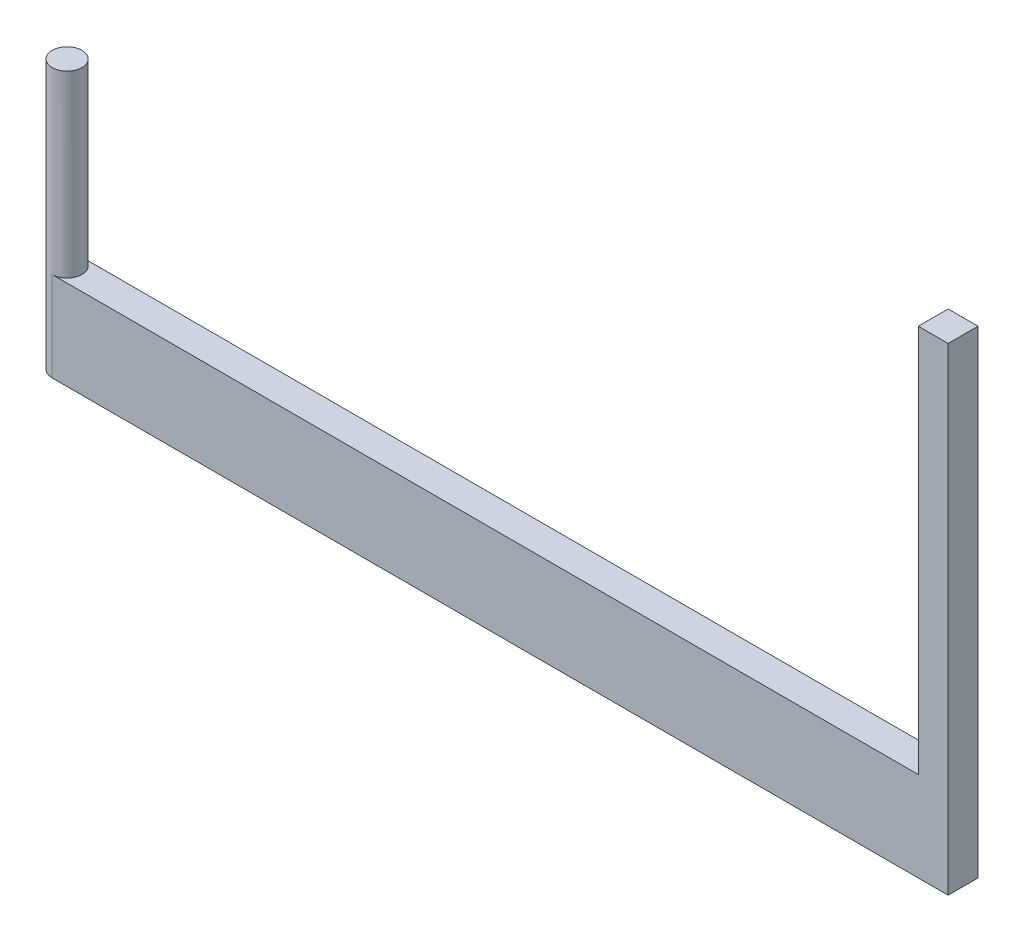
SolidWorks part; units mm, degrees
ref_plane "Front Plane" through (0, 0, 0) normal (0, 0, 1) x (1, 0, 0)
ref_plane "Top Plane" through (0, 0, 0) normal (0, 1, 0) x (1, 0, 0)
ref_plane "Right Plane" through (0, 0, 0) normal (1, 0, 0) x (0, 0, -1)
sketch "Sketch1" plane through (0, 0, 0) normal (0, 1, 0) x (1, 0, 0)
  line L0 (0, 0) -> (0, 2.5) construction
  line L1 (0, 2.5) -> (150, 2.5) construction
  line L2 (150, 2.5) -> (150, -2.5) construction
  line L3 (150, -2.5) -> (0, -2.5) construction
  line L4 (0, -2.5) -> (0, 2.5) construction
  line L5 (0, 2.5) -> (150, 2.5)
  line L6 (150, 2.5) -> (150, -2.5)
  line L7 (150, -2.5) -> (0, -2.5)
  circle A0 centre (0, 0) radius 2.5
extrude "Boss-Extrude1" add sketch "Sketch1" along normal blind 45 contours A0
extrude "Boss-Extrude2" add sketch "Sketch1<3>" along normal blind 15 contours A0 L7 L6 L5 region at (75.9807, 0, 0)
sketch "Sketch1<3>" plane through (0, 0, 0) normal (0, 1, 0) x (1, 0, 0) same geometry as "Sketch1"
ref_plane "Plane2" through (0, 0, 2.5) normal (0, 0, 1) x (1, 0, 0)
sketch "Sketch3" plane through (0, 0, 2.5) normal (0, 0, 1) x (1, 0, 0)
  line L0 (150, 15) -> (150, 80)
  line L1 (150, 80) -> (145, 80)
  line L2 (145, 80) -> (145, 15)
  line L3 (150, 15) -> (0, 15) construction
  line L4 (145, 15) -> (150, 15)
extrude "Boss-Extrude5" add sketch "Sketch3" against normal blind 5
sketch "Sketch4" plane through (0, 0, 2.5) normal (0, 0, 1) x (1, 0, 0)
  line L0 (145, 80) -> (150, 80)
  line L1 (150, 80) -> (150, 0)
  line L2 (150, 0) -> (145, 0)
  line L3 (150, 0) -> (0, 0) construction
  line L4 (145, 0) -> (145, 80)
